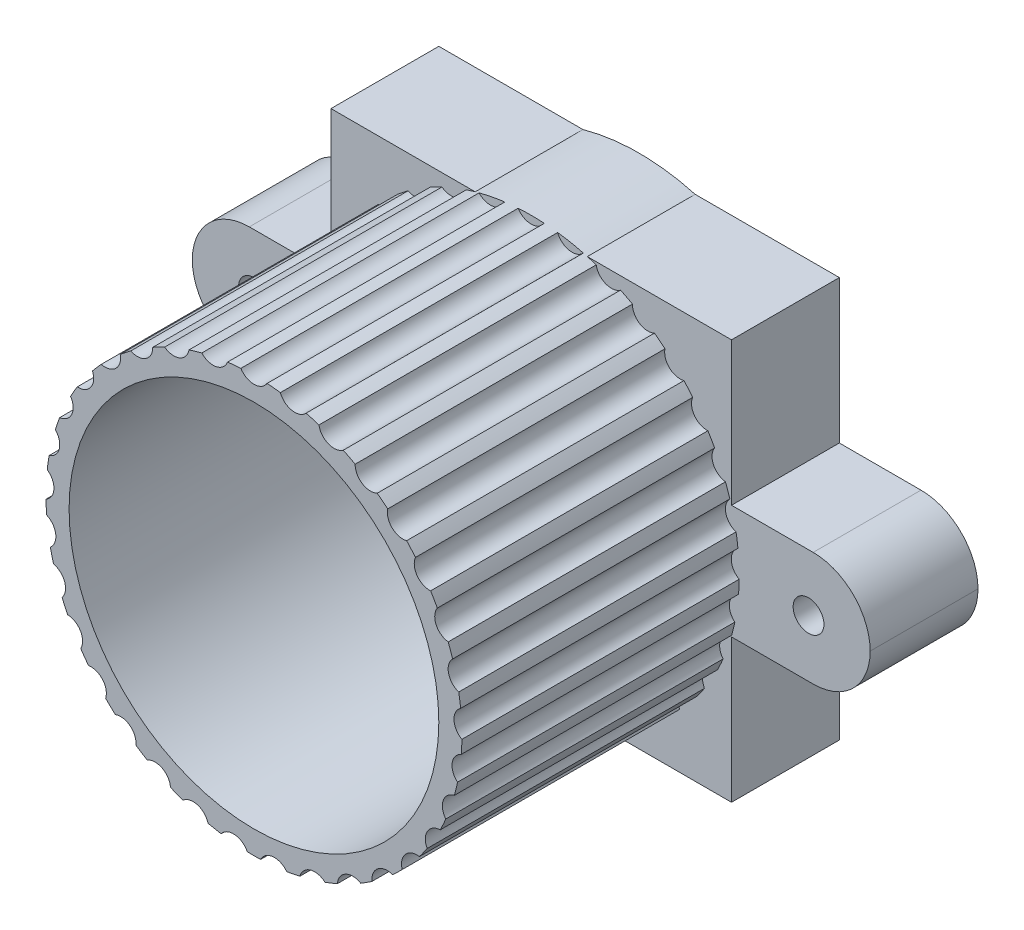
SolidWorks part; units mm, degrees
ref_plane "Front Plane" through (0, 0, 0) normal (0, 0, 1) x (1, 0, 0)
ref_plane "Top Plane" through (0, 0, 0) normal (0, 1, 0) x (1, 0, 0)
ref_plane "Right Plane" through (0, 0, 0) normal (1, 0, 0) x (0, 0, -1)
sketch "Sketch1" plane through (0, 0, 0) normal (0, 0, 1) x (1, 0, 0)
  line L1 (-6.5, 6.5) -> (6.5, 6.5)
  line L2 (-6.5, 6.5) -> (-6.5, -6.5)
  line L3 (-6.5, -6.5) -> (6.5, -6.5)
  line L4 (6.5, 6.5) -> (6.5, -6.5)
  line L5 (-6.5, 6.5) -> (6.5, -6.5) construction
  line L6 (-6.5, -6.5) -> (6.5, 6.5) construction
  point P0 (0, 0)
  dimension "D1" = 13
  dimension "D2" = 13
extrude "Boss-Extrude1" add sketch "Sketch1" along normal blind 3.5
sketch "Sketch2" plane through (0, 0, 3.5) normal (0, 0, 1) x (1, 0, 0)
  line L1 (-11, 1.85) -> (11, 1.85)
  line L2 (-11, 1.85) -> (-11, -1.85)
  line L3 (-11, -1.85) -> (11, -1.85)
  line L4 (11, 1.85) -> (11, -1.85)
  line L5 (-11, 1.85) -> (11, -1.85) construction
  line L6 (-11, -1.85) -> (11, 1.85) construction
  point P0 (0, 0)
  dimension "D1" = 22
  dimension "D2" = 3.7
extrude "Boss-Extrude2" add sketch "Sketch2" against normal blind 3.5
fillet "Fillet1" radius 1.85 4 edges at (11, -1.85, 1.75) (11, 1.85, 1.75) (-11, -1.85, 1.75) (-11, 1.85, 1.75)
sketch "Sketch3" plane through (0, 0, 3.5) normal (0, 0, 1) x (1, 0, 0)
  circle A0 centre (-9, 0) radius 0.5
  circle A1 centre (9, 0) radius 0.5
  dimension "D1" = 1
  dimension "D2" = 1
  dimension "D3" = 18
  dimension "D4" = 9
extrude "Cut-Extrude1" cut sketch "Sketch3" against normal blind 3.5
sketch "Sketch4" plane through (0, 0, 3.5) normal (0, 0, 1) x (1, 0, 0)
  circle A0 centre (0, 0) radius 6.75
  dimension "D1" = 13.5
extrude "Boss-Extrude3" add sketch "Sketch4" along normal blind 9 and the other way blind 3.5
sketch "Sketch5" plane through (0, 0, 12.5) normal (0, 0, 1) x (1, 0, 0)
  circle A0 centre (0, 7) radius 0.5
  circle A1 centre (1.3248, 6.8735) radius 0.5
  circle A2 centre (2.6016, 6.4986) radius 0.5
  circle A3 centre (3.7845, 5.8888) radius 0.5
  circle A4 centre (4.8306, 5.0661) radius 0.5
  circle A5 centre (5.702, 4.0604) radius 0.5
  circle A6 centre (6.3674, 2.9079) radius 0.5
  circle A7 centre (6.8027, 1.6503) radius 0.5
  circle A8 centre (6.9921, 0.3331) radius 0.5
  circle A9 centre (6.9288, -0.9962) radius 0.5
  circle A10 centre (6.615, -2.2895) radius 0.5
  circle A11 centre (6.0622, -3.5) radius 0.5
  circle A12 centre (5.2902, -4.584) radius 0.5
  circle A13 centre (4.3271, -5.5024) radius 0.5
  circle A14 centre (3.2076, -6.2218) radius 0.5
  circle A15 centre (1.9721, -6.7165) radius 0.5
  circle A16 centre (0.6654, -6.9683) radius 0.5
  circle A17 centre (-0.6654, -6.9683) radius 0.5
  circle A18 centre (-1.9721, -6.7165) radius 0.5
  circle A19 centre (-3.2076, -6.2218) radius 0.5
  circle A20 centre (-4.3271, -5.5024) radius 0.5
  circle A21 centre (-5.2902, -4.584) radius 0.5
  circle A22 centre (-6.0622, -3.5) radius 0.5
  circle A23 centre (-6.615, -2.2895) radius 0.5
  circle A24 centre (-6.9288, -0.9962) radius 0.5
  circle A25 centre (-6.9921, 0.3331) radius 0.5
  circle A26 centre (-6.8027, 1.6503) radius 0.5
  circle A27 centre (-6.3674, 2.9079) radius 0.5
  circle A28 centre (-5.702, 4.0604) radius 0.5
  circle A29 centre (-4.8306, 5.0661) radius 0.5
  circle A30 centre (-3.7845, 5.8888) radius 0.5
  circle A31 centre (-2.6016, 6.4986) radius 0.5
  circle A32 centre (-1.3248, 6.8735) radius 0.5
  point P69 (0, 0)
  dimension "D1" = 1
  dimension "D2" = 7
  dimension "D3" = 33
extrude "Cut-Extrude2" cut sketch "Sketch5" against normal blind 9
sketch "Sketch6" plane through (0, 0, 12.5) normal (0, 0, 1) x (1, 0, 0)
  circle A0 centre (0, 0) radius 6
  dimension "D1" = 12
extrude "Cut-Extrude3" cut sketch "Sketch6" against normal blind 9
